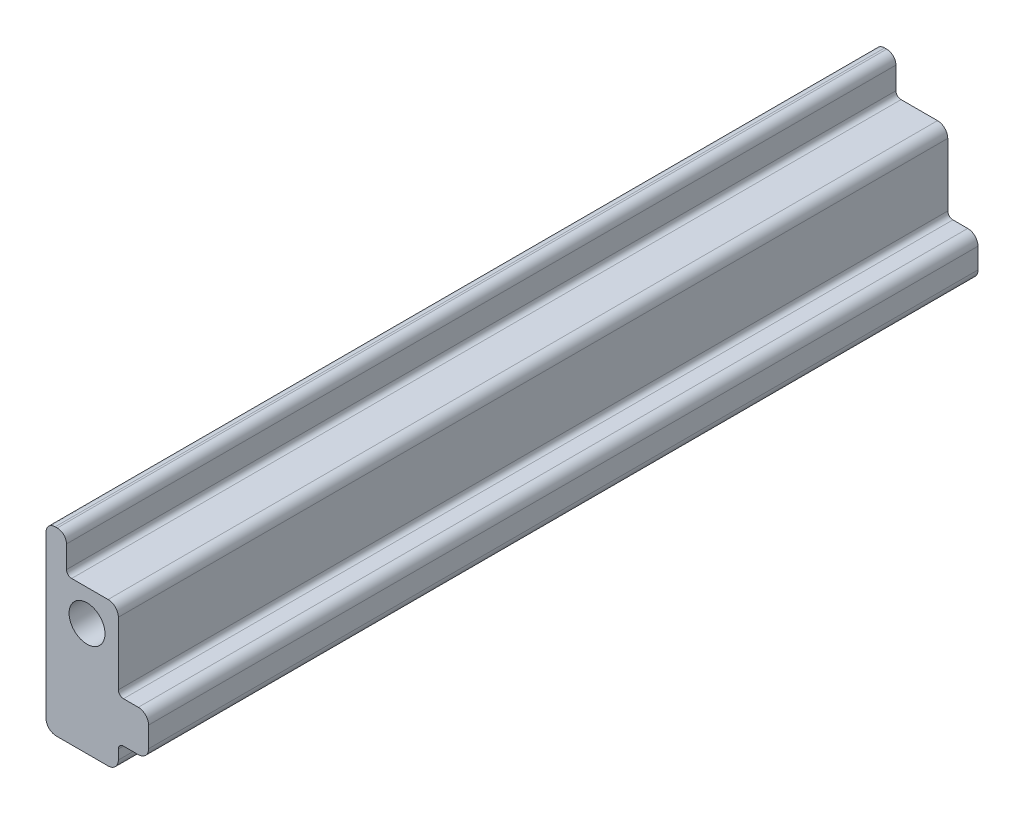
SolidWorks part; units mm, degrees
material "Pink Foam"
ref_plane "Front Plane" through (0, 0, 0) normal (0, 0, 1) x (1, 0, 0)
ref_plane "Top Plane" through (0, 0, 0) normal (0, 1, 0) x (1, 0, 0)
ref_plane "Right Plane" through (0, 0, 0) normal (1, 0, 0) x (0, 0, -1)
sketch "Sketch1" plane through (0, 0, 0) normal (0, 0, 1) x (1, 0, 0)
  line L1 (13.0378, -69.85) -> (-19.05, -69.85)
  line L2 (38.1, -48.0972) -> (38.1, -35.3972)
  line L3 (31.75, -29.0472) -> (22.5628, -29.0472)
  line L4 (-25.4, -63.5) -> (-25.4, 36.2978)
  line L6 (19.3878, -25.8722) -> (19.3878, 13.0378)
  line L7 (13.0378, 19.3878) -> (-9.525, 19.3878)
  line L8 (-12.7, 22.5628) -> (-12.7, 36.2978)
  line L9 (-18.415, 42.0128) -> (-19.685, 42.0128)
  line L11 (31.75, -54.4472) -> (22.5628, -54.4472)
  line L12 (11.1125, 0) -> (19.3878, 0) construction
  line L14 (0, 11.1125) -> (0, 19.3878) construction
  line L15 (19.3878, -57.6222) -> (19.3878, -63.5)
  circle A0 centre (0, 0) radius 11.1125
  arc A3 (-9.525, 19.3878) -> (-12.7, 22.5628) centre (-9.525, 22.5628) cw
  arc A4 (-19.05, -69.85) -> (-25.4, -63.5) centre (-19.05, -63.5) cw
  arc A6 (38.1, -35.3972) -> (31.75, -29.0472) centre (31.75, -35.3972) ccw
  arc A8 (19.3878, 13.0378) -> (13.0378, 19.3878) centre (13.0378, 13.0378) ccw
  arc A9 (-12.7, 36.2978) -> (-18.415, 42.0128) centre (-18.415, 36.2978) ccw
  arc A10 (-19.685, 42.0128) -> (-25.4, 36.2978) centre (-19.685, 36.2978) ccw
  arc A11 (19.3878, -25.8722) -> (22.5628, -29.0472) centre (22.5628, -25.8722) ccw
  arc A12 (22.5628, -54.4472) -> (19.3878, -57.6222) centre (22.5628, -57.6222) ccw
  arc A13 (31.75, -54.4472) -> (38.1, -48.0972) centre (31.75, -48.0972) ccw
  arc A14 (19.3878, -63.5) -> (13.0378, -69.85) centre (13.0378, -63.5) cw
  point P9 (0, -11.1125)
  point P15 (0, 11.1125)
  point P16 (11.1125, 0)
  point P31 (-12.7, 19.3878)
  point P34 (-25.4, -69.85)
  point P37 (38.1, -69.85)
  point P40 (38.1, -29.0472)
  point P47 (-12.7, 42.0128)
  point P50 (-25.4, 42.0128)
  dimension "D1" = 22.225
  dimension "D6" = 8.2753
  dimension "D10" = 3.175
  dimension "D11" = 6.35
  dimension "D12" = 5.715
  dimension "D5" = 3.175
  dimension "D7" = 6.35
  dimension "D13" = 29.0472
  dimension "D14" = 3.175
  dimension "D15" = 3.175
  dimension "D16" = 6.35
  dimension "D17" = 6.35
  dimension "D18" = 25.4
  dimension "D2" = 63.5
  dimension "D3" = 69.85
  dimension "D4" = 25.4
  dimension "D8" = 22.625
  dimension "D9" = 12.7
  dimension "D19" = 18.7122
extrude "Boss-Extrude1" add sketch "Sketch1" along normal blind 513.461
